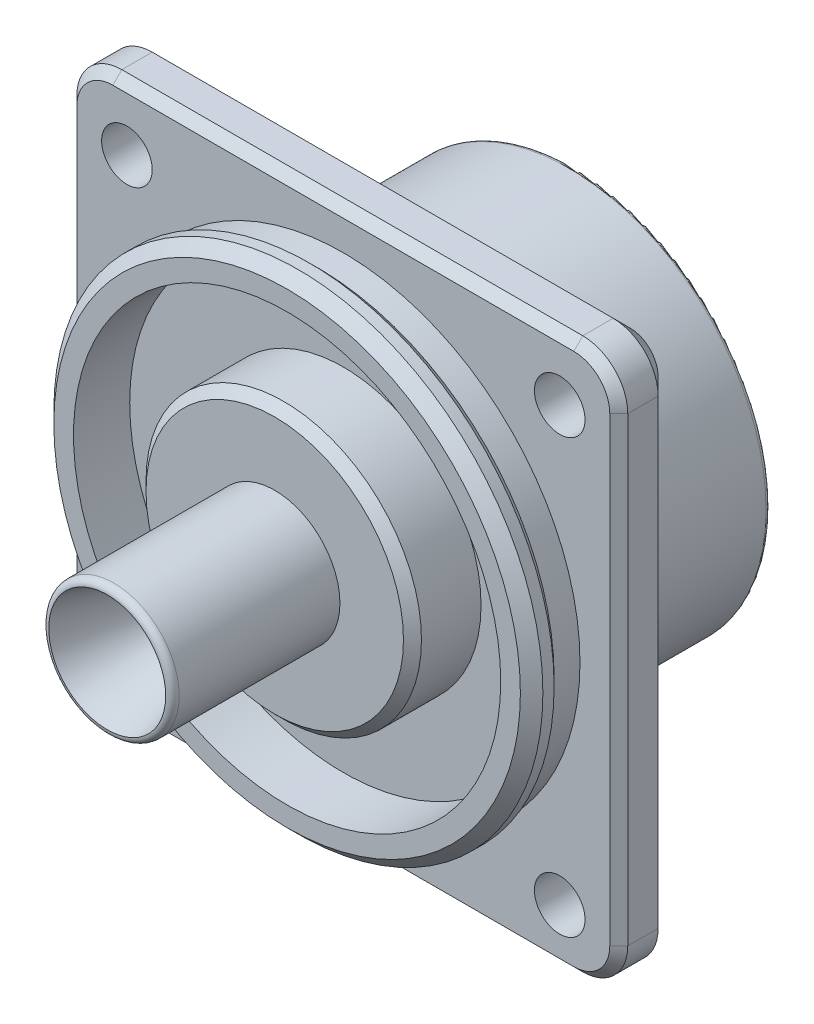
SolidWorks part; units mm, degrees
ref_plane "前视基准面" through (0, 0, 0) normal (0, 0, 1) x (1, 0, 0)
ref_plane "上视基准面" through (0, 0, 0) normal (0, 1, 0) x (1, 0, 0)
ref_plane "右视基准面" through (0, 0, 0) normal (1, 0, 0) x (0, 0, -1)
sketch "草图1" plane through (0, 0, 0) normal (0, 1, 0) x (1, 0, 0)
  line L0 (0, 0) -> (0, 34.5672) construction
  line L5 (0, 35.6444) -> (0, 50.2816) construction
  line L6 (0, 35.6444) -> (-3.9, 35.6444)
  line L7 (0, 35.6444) -> (0, -5.8556)
  line L8 (-5.2, -5.8556) -> (-5.8, -5.8556)
  line L9 (-17.5, 35.6444) -> (-17.5, 20.1444)
  line L10 (-5.8, -5.8556) -> (-5.2, -5.8556)
  line L11 (-5.8, -5.8556) -> (-5.8, 9.0444)
  line L13 (0, -5.8556) -> (0, 9.0444)
  line L14 (-5.8, 9.0444) -> (-12.25, 9.0444)
  line L15 (0, 9.0444) -> (0, 17.1444)
  line L17 (-12.25, 9.0444) -> (-12.25, 17.1444)
  line L19 (-12.25, 9.0444) -> (-12.25, 17.1444)
  line L21 (-19, 10.1444) -> (-19, 17.1444)
  line L22 (-19, 10.1444) -> (-21.05, 10.1444)
  line L23 (-19, 10.1444) -> (-19, 15.1444)
  line L25 (-21.05, 10.1444) -> (-21.05, 15.1444)
  line L27 (-19, 17.1444) -> (-19, 15.1444)
  line L28 (-21.05, 15.1444) -> (-24.5, 15.1444)
  line L30 (-17.5, 20.1444) -> (-24.5, 20.1444)
  line L34 (-21.05, 10.1444) -> (-21.75, 10.1444)
  line L35 (-21.05, 10.1444) -> (-21.05, 12.9444)
  line L36 (-21.05, 12.9444) -> (-21.75, 12.9444)
  line L37 (-21.75, 10.1444) -> (-21.75, 12.9444)
  line L40 (-5.85, 35.6444) -> (-5.85, 34.5444)
  line L41 (-5.85, 34.5444) -> (-3.9, 34.5444)
  line L42 (-3.9, 35.6444) -> (-3.9, 34.5444)
  line L43 (-24.5, 20.1444) -> (-24.5, 15.1444)
  line L44 (-19, 17.1444) -> (-12.25, 17.1444)
  line L45 (-5.85, 35.6444) -> (-17.5, 35.6444)
  line L46 (0, 13.0535) -> (-5.2, -5.8556)
  line L47 (-3, 2.1444) -> (0, 2.1444)
  point P7 (0, 0)
  point P20 (-5.85, 35.0944)
  point P23 (0, 13.0535)
  dimension "D1" = 17.5
  dimension "D2" = 21.75
  dimension "D20" = 8
  dimension "D3" = 21.05
  dimension "D4" = 19
  dimension "D5" = 12.25
  dimension "D6" = 5.8
  dimension "D7" = 7
  dimension "D8" = 15.5
  dimension "D9" = 20.5
  dimension "D10" = 1.1
  dimension "D11" = 3.9
  dimension "D12" = 24.5
  dimension "D13" = 5.85
  dimension "D14" = 41.5
  dimension "D15" = 2.2
  dimension "D16" = 5
  dimension "D17" = 6.1
  dimension "D18" = 3
  dimension "D19" = 5.2
revolve "旋转1" add sketch "草图1" angle 360 about L5 region at (-8.956, 0, -21.1533) region at (-21.4, 0, -11.5444)
fillet "圆角3" radius 0.6 1 edges at (5.8, 0, 5.8556)
sketch "草图2" plane through (0, 0, 0) normal (0, 1, 0) x (1, 0, 0)
  line L1 (-24.5, 20.1444) -> (24.5, 20.1444)
  line L2 (-24.5, 20.1444) -> (-24.5, 15.1444)
  line L3 (-24.5, 15.1444) -> (24.5, 15.1444)
  line L4 (24.5, 20.1444) -> (24.5, 15.1444)
extrude "凸台-拉伸1" add sketch "草图2" along normal mid plane 49
fillet "圆角4" radius 4 4 edges at (-24.5, 24.5, -17.6444) (-24.5, -24.5, -17.6444) (24.5, -24.5, -17.6444) (24.5, 24.5, -17.6444)
chamfer "倒角3" distance 1.5 angle 45 8 edges at (23.3284, -23.3284, -20.1444) (24.5, 0, -20.1444) (23.3284, 23.3284, -20.1444) (0, 24.5, -20.1444) (-23.3284, 23.3284, -20.1444) (-24.5, 0, -20.1444) (-23.3284, -23.3284, -20.1444) (0, -24.5, -20.1444)
chamfer "倒角4" distance 1 angle 45 1 edges at (21.75, 0, -10.1444)
ref_plane "基准面1" through (0, 0, -35.6444) normal (0, 0, -1) x (-1, 0, 0)
sketch "草图3" plane through (0, 0, -35.6444) normal (0, 0, -1) x (-1, 0, 0)
  circle A0 centre (0, 0) radius 3
  dimension "D1" = 6
extrude "切除-拉伸1" cut sketch "草图3" against normal through all
sketch "草图4" plane through (0, 0, -35.6444) normal (0, 0, -1) x (-1, 0, 0)
  line L0 (0, 0) -> (0, 29.8811) construction
  line L1 (0, 0) -> (9.7602, 0) construction
  circle A0 centre (-19.25, 18.9318) radius 2.25
  circle A1 centre (19.25, 18.9318) radius 2.25
  circle A2 centre (-19.25, -19.5682) radius 2.25
  circle A3 centre (19.25, -19.5682) radius 2.25
  dimension "D5" = 4.5
  dimension "D6" = 4.5
  dimension "D7" = 4.5
  dimension "D8" = 4.5
  dimension "D1" = 38.5
  dimension "D2" = 38.5
  dimension "D3" = 38.5
  dimension "D4" = 19.25
extrude "切除-拉伸2" cut sketch "草图4" against normal through all
sketch "草图5" plane through (0, 0, -35.6444) normal (0, 0, -1) x (-1, 0, 0)
  circle A0 centre (-8.5, 8.5) radius 2
  circle A1 centre (8.5, 8.5) radius 2
  circle A2 centre (8.5, -8.5) radius 2
  circle A3 centre (-8.5, -8.5) radius 2
  point P0 (0, 0)
  dimension "D3" = 4
  dimension "D4" = 4
  dimension "D5" = 4
  dimension "D6" = 4
  dimension "D1" = 17
  dimension "D2" = 17
extrude "切除-拉伸3" cut sketch "草图5" against normal blind 9
cosmetic thread "装饰螺纹线1" parameters "D1"=6, "D2"=5
cosmetic thread "装饰螺纹线2" parameters "D1"=6, "D2"=5
cosmetic thread "装饰螺纹线3" parameters "D1"=6, "D2"=5
cosmetic thread "装饰螺纹线4" parameters "D1"=6, "D2"=5
fillet "圆角7" radius 0.4 1 edges at (17.5, 0, -35.6444)
chamfer "倒角5" distance 0.8 angle 45 1 edges at (12.25, 0, -9.0444)
chamfer "倒角6" distance 0.8 angle 45 1 edges at (21.75, 0, -12.9444)
chamfer "倒角7" distance 0.8 angle 45 8 edges at (23.3284, 23.3284, -15.1444) (24.5, 0, -15.1444) (23.3284, -23.3284, -15.1444) (0, -24.5, -15.1444) (-23.3284, -23.3284, -15.1444) (-24.5, 0, -15.1444) (-23.3284, 23.3284, -15.1444) (0, 24.5, -15.1444)
